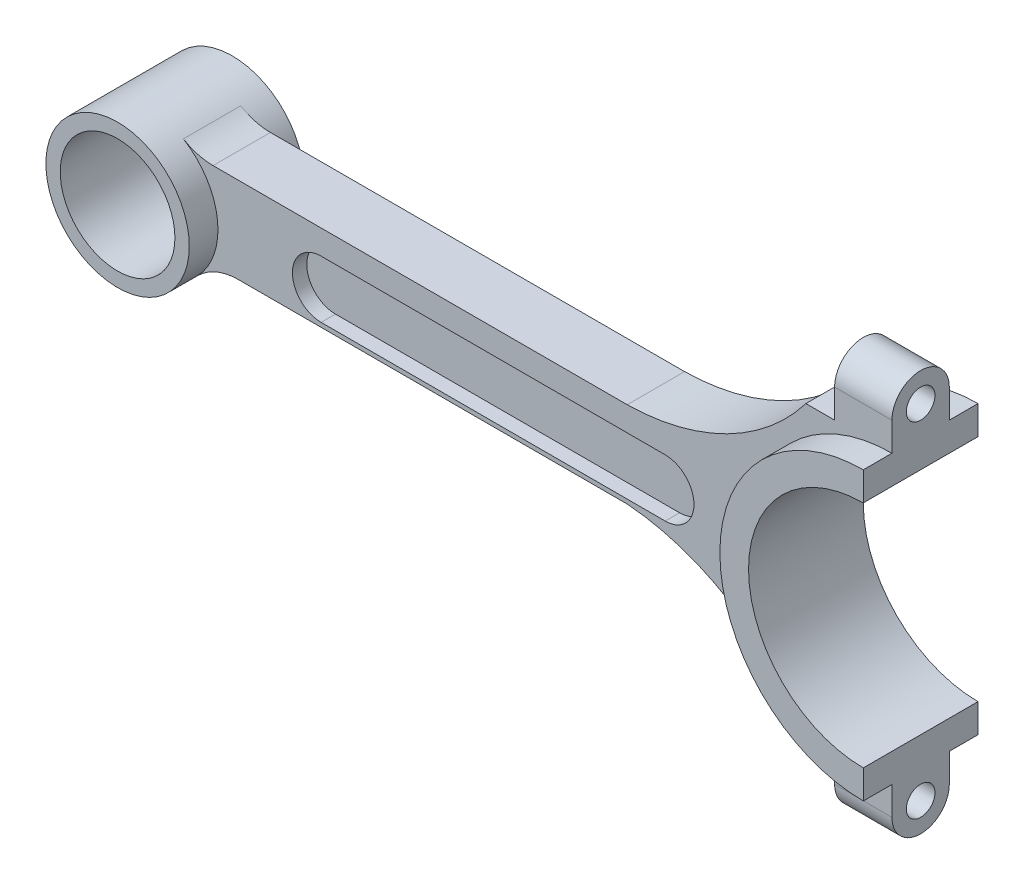
SolidWorks part; units mm, degrees
material "Cast Carbon Steel"
ref_plane "Front Plane" through (0, 0, 0) normal (0, 0, 1) x (1, 0, 0)
ref_plane "Top Plane" through (0, 0, 0) normal (0, 1, 0) x (1, 0, 0)
ref_plane "Right Plane" through (0, 0, 0) normal (1, 0, 0) x (0, 0, -1)
sketch "Sketch2" plane through (0, 0, 0) normal (0, 0, 1) x (1, 0, 0)
  line L10 (14.7936, 11.7475) -> (106.4857, 11.7475)
  line L12 (106.4819, -7.3025) -> (20.4066, -7.3025)
  line L14 (165.1, -25.4) -> (165.1, -31.75)
  line L15 (38.7124, 0) -> (114.9124, 0) construction
  line L16 (38.7124, 6.35) -> (114.9124, 6.35)
  line L17 (38.7124, -6.35) -> (114.9124, -6.35)
  line L20 (146.05, 31.75) -> (165.1, 31.75)
  line L21 (165.1, -31.75) -> (146.05, -31.75)
  line L25 (165.1, 31.75) -> (165.1, 25.4)
  circle A0 centre (0, 0) radius 15.875
  circle A1 centre (0, 0) radius 12.7
  arc A5 (8.2187, 13.5819) -> (14.7936, 11.7475) centre (14.7936, 24.4475) ccw
  arc A6 (20.4066, -7.3025) -> (11.337, -11.1125) centre (20.4066, -20.0025) ccw
  arc A8 (165.1, 25.4) -> (165.1, -25.4) centre (165.1, 0) ccw
  arc A11 (38.7124, 6.35) -> (38.7124, -6.35) centre (38.7124, 0) ccw
  arc A12 (114.9124, -6.35) -> (114.9124, 6.35) centre (114.9124, 0) ccw
  arc A13 (106.4857, 11.7475) -> (146.05, 31.75) centre (105.6495, 62.5311) ccw
  arc A14 (146.05, -31.75) -> (106.4819, -7.3025) centre (102.5322, -57.9392) ccw
  arc A15 (165.1, 31.75) -> (165.1, -31.75) centre (165.1, 0) ccw
  point P20 (76.8124, 0)
  dimension "D1" = 31.75
  dimension "D2" = 25.4
  dimension "D4" = 19.05
  dimension "D3" = 19.05
  dimension "D6" = 25.4
  dimension "D5" = 165.1
  dimension "D8" = 19.05
  dimension "D9" = 76.2
  dimension "D10" = 12.7
extrude "Boss-Extrude2" add sketch "Sketch2" along normal mid plane 12.7 contours L10 A5 A0 A6 L12 A12 L17 A11 L16 region at (60.6396, 10.055, 0)
extrude "Boss-Extrude3" add sketch "Sketch2<8>" along normal mid plane 25.4 contours A0 A1 | L25 A15 L14 A8 region at (13.4379, 7.5752, 0) region at (164.39, 28.575, 0)
sketch "Sketch2<8>" plane through (0, 0, 0) normal (0, 0, 1) x (1, 0, 0) same geometry as "Sketch2"
extrude "Boss-Extrude4" add sketch "Sketch2<9>" along normal mid plane 6.35 contours L17 A12 L16 A11 region at (76.8124, 0, 0)
sketch "Sketch2<9>" plane through (0, 0, 0) normal (0, 0, 1) x (1, 0, 0) same geometry as "Sketch2"
sketch "Sketch3" plane through (165.1, 0, 0) normal (1, 0, 0) x (0, 0, -1)
  line L1 (-6.35, 31.75) -> (6.35, 31.75)
  line L2 (-6.35, 31.75) -> (-6.35, 38.0851)
  line L4 (6.35, 31.75) -> (6.35, 38.0851)
  line L5 (-6.35, -31.75) -> (6.35, -31.75)
  line L9 (-6.35, -31.75) -> (-6.35, -38.0584)
  line L15 (6.35, -31.75) -> (6.35, -38.0584)
  arc A0 (6.35, 38.0851) -> (-6.35, 38.0851) centre (0, 38.0851) ccw
  arc A1 (-0.4344, 31.75) -> (0.4344, 31.75) centre (0, 38.0851) ccw
  circle A2 centre (0, 38.0851) radius 3.175
  arc A3 (0.7254, -31.75) -> (-0.7254, -31.75) centre (0, -38.0584) ccw
  arc A4 (-6.35, -38.0584) -> (6.35, -38.0584) centre (0, -38.0584) ccw
  circle A5 centre (0, -38.0584) radius 3.175
  dimension "D1" = 12.7
extrude "Boss-Extrude6" add sketch "Sketch3" against normal blind 12.7 contours L4 A0 L2 L1 A2 | L9 A4 L15 L5 A5 region at (165.1, 34.9176, 6.1705) region at (165.1, -31.9293, 3.5377)
